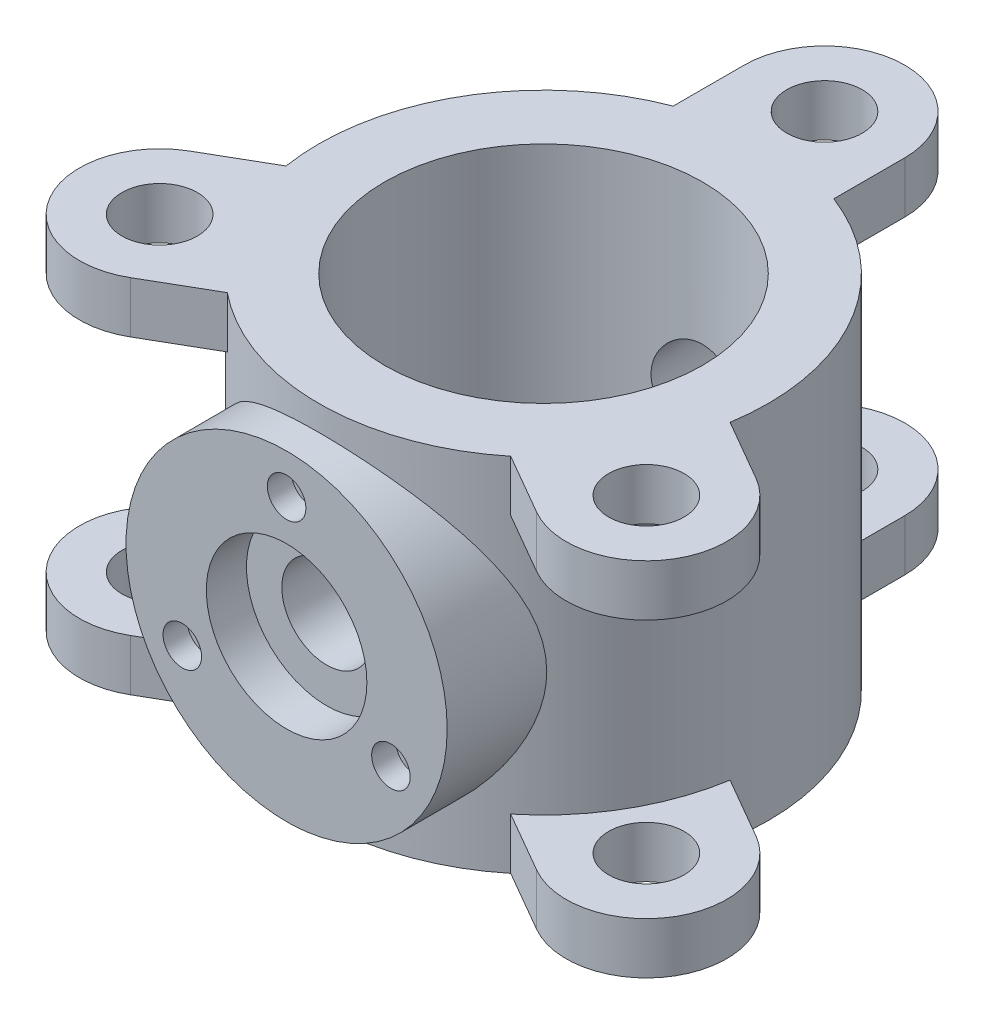
SolidWorks part; units mm, degrees
note: '?' marks a value the reader was unsure of.
ref_plane "Front Plane" through (0, 0, 0) normal (0, 0, 1) x (1, 0, 0)
ref_plane "Top Plane" through (0, 0, 0) normal (0, 1, 0) x (1, 0, 0)
ref_plane "Right Plane" through (0, 0, 0) normal (1, 0, 0) x (0, 0, -1)
sketch "Sketch1" plane through (0, 0, 0) normal (0, 1, 0) x (1, 0, 0)
  circle A0 centre (0, 0) radius 97
  circle A1 centre (0, 0) radius 140
extrude "Boss-Extrude1" add sketch "Sketch1" along normal blind 225 contours A1
sketch "Sketch2" plane through (0, 225, 0) normal (0, 1, 0) x (1, 0, 0)
  circle A0 centre (0, 0) radius 99
  dimension "D1" = 198
extrude "Cut-Extrude1" cut sketch "Sketch2" against normal through all
sketch "Sketch3" plane through (0, 225, 0) normal (0, 1, 0) x (1, 0, 0)
  line L0 (-50, 175) -> (-50, 130.767)
  line L6 (-23.5, 175) -> (-23.5, 173.415)
  line L8 (23.5, 175) -> (23.5, 173.415)
  line L9 (50, 175) -> (50, 130.767)
  circle A1 centre (0, 175) radius 23.5
  circle A3 centre (0, 0) radius 140 construction
  arc A5 (50, 175) -> (-49.4872, 167.8571) centre (0, 175) ccw
extrude "Boss-Extrude2" add sketch "Sketch3" against normal blind 32
ref_axis "Axis1" through (0, 225, 0) along (0, -1, 0)
pattern_circular "CirPattern1" count 3 over 360 about axis through (0, 0, 0) along (0, 1, 0) of "Boss-Extrude2"
ref_plane "Plane1" through (0, 112.5, 0) normal (0, -1, 0) x (-1, 0, 0)
mirror "Mirror3" about plane through (0, 112.5, 0) normal (0, -1, 0) of "Boss-Extrude2"
pattern_circular "CirPattern2" count 3 over 360 about axis through (0, 225, 0) along (0, -1, 0) of "Mirror3"
ref_plane "Plane2" through (0, 0, 160) normal (0, 0, 1) x (1, 0, 0)
sketch "Sketch5" plane through (0, 0, 160) normal (0, 0, 1) x (1, 0, 0)
  line L0 (0, 225) -> (0, 0) construction
  circle A0 centre (0, 109.3901) radius 100
  dimension "D1" = 200
extrude "Boss-Extrude3" add sketch "Sketch5" against normal up to next
sketch "Sketch6" plane through (0, 0, 160) normal (0, 0, 1) x (1, 0, 0)
  circle A0 centre (0, 109.3901) radius 50
  dimension "D1" = 100
extrude "Cut-Extrude2" cut sketch "Sketch6" against normal blind 25
sketch "Sketch9" plane through (0, 0, 160) normal (0, 0, 1) x (1, 0, 0)
  circle A0 centre (0, 109.3901) radius 28
  dimension "D1" = 56
extrude "Cut-Extrude3" cut sketch "Sketch9" against normal through all
sketch "Sketch11" plane through (0, 0, 160) normal (0, 0, 1) x (1, 0, 0)
  circle A0 centre (0, 109.3901) radius 75 construction
  circle A1 centre (0, 184.3901) radius 12
ref_plane "Plane3" through (0, 109.3901, 0) normal (0, 1, 0) x (1, 0, 0)
extrude "Cut-Extrude4" cut sketch "Sketch11" against normal blind 15 contours A1
ref_axis "Axis2" through (0, 109.3901, 93.3009) along (0, 0, 1)?
pattern_circular "CirPattern4" count 3 over 360 about axis through (0, 109.3901, 0) along (0, 0, 1) of "Cut-Extrude4"
